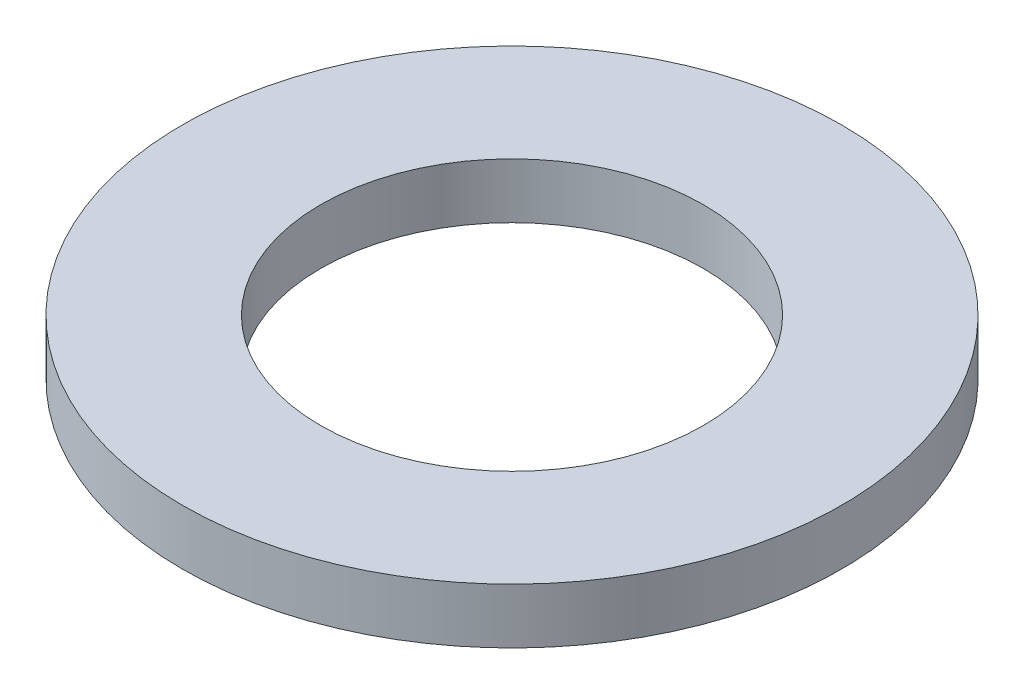
SolidWorks part; units mm, degrees
ref_plane "Front Plane" through (0, 0, 0) normal (0, 0, 1) x (1, 0, 0)
ref_plane "Top Plane" through (0, 0, 0) normal (0, 1, 0) x (1, 0, 0)
ref_plane "Right Plane" through (0, 0, 0) normal (1, 0, 0) x (0, 0, -1)
sketch "Sketch1" plane through (0, 0, 0) normal (0, 1, 0) x (1, 0, 0)
  circle A0 centre (0, 0) radius 77.5
  dimension "FLANGE_OD" = 155
extrude "Boss-Extrude1" add sketch "Sketch1" along normal blind 13
sketch "Sketch2" plane through (0, 0, 0) normal (0, 1, 0) x (1, 0, 0)
  circle A0 centre (0, 0) radius 45
  dimension "BORE_D" = 90
extrude "Cut-Extrude1" cut sketch "Sketch2" along normal through all
sketch "Sketch3" plane through (0, 13, 0) normal (0, 1, 0) x (1, 0, 0)
  circle A0 centre (0, 0) radius 26.6223 construction
  circle A1 centre (-26.6223, 0) radius 2.5279
  dimension "BOLT_D" = 5.0558
  dimension "BOLT_PCD" = 53.2446
extrude "Cut-Extrude2" cut sketch "Sketch3" against normal blind 10.8245 rebuild error yes
pattern_circular "CirPattern1" count 3 over 360 rebuild error yes
